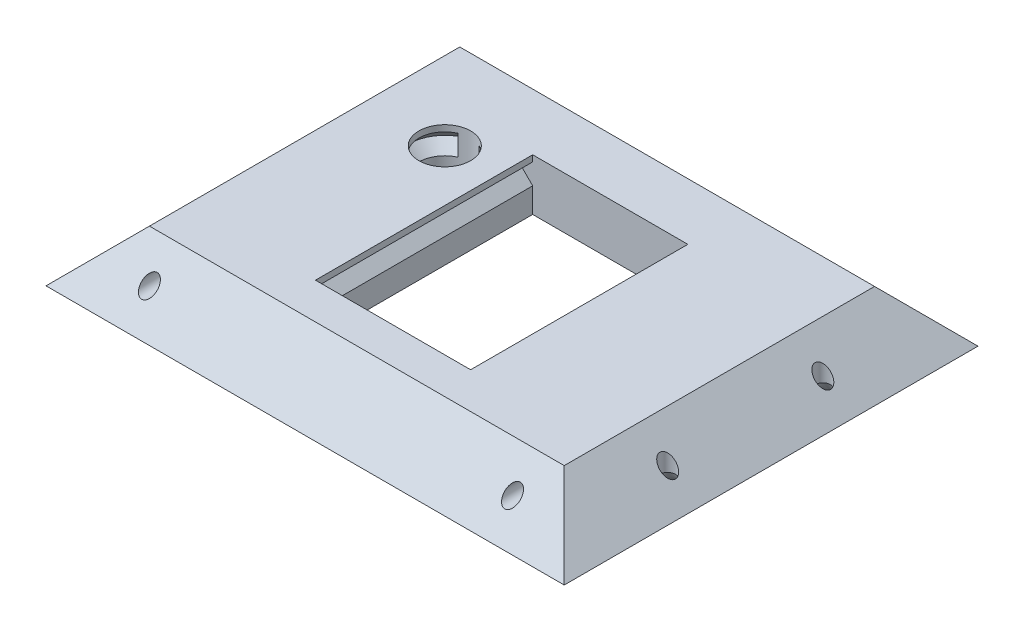
SolidWorks part; units mm, degrees
ref_plane "Спереди" through (0, 0, 0) normal (0, 0, 1) x (1, 0, 0)
ref_plane "Сверху" through (0, 0, 0) normal (0, 1, 0) x (1, 0, 0)
ref_plane "Справа" through (0, 0, 0) normal (1, 0, 0) x (0, 0, -1)
sketch "Эскиз1" plane through (0, 0, 0) normal (0, 1, 0) x (1, 0, 0)
  line L1 (-50.1, -40) -> (50.1, -40)
  line L2 (-50.1, -40) -> (-50.1, 40)
  line L3 (-50.1, 40) -> (50.1, 40)
  line L4 (50.1, -40) -> (50.1, 40)
  line L5 (-50.1, -40) -> (50.1, 40) construction
  line L6 (-50.1, 40) -> (50.1, -40) construction
  point P0 (0, 0)
  dimension "D1" = 100.2
  dimension "D2" = 80
ref_plane "Плоскость1" through (0, 10, 0) normal (0, 1, 0) x (1, 0, 0)
sketch "Эскиз2" plane through (0, 10, 0) normal (0, 1, 0) x (1, 0, 0)
  line L4 (50.1, -40) -> (50.1, 40) construction
  line L5 (-50.1, -40) -> (50.1, -40) construction
  line L6 (-50.1, -40) -> (-50.1, 40) construction
  line L7 (-50.1, 40) -> (50.1, 40) construction
  line L8 (40.1, -30) -> (40.1, 30)
  line L9 (-40.1, -30) -> (40.1, -30)
  line L10 (-40.1, 30) -> (-40.1, -30)
  line L11 (40.1, 30) -> (-40.1, 30)
  line L12 (40.1, -30) -> (40.1, 30)
  line L13 (-40.1, -30) -> (40.1, -30)
  line L14 (-40.1, 30) -> (-40.1, -30)
  line L15 (40.1, 30) -> (-40.1, 30)
  line L16 (50.1, -40) -> (50.1, 40) construction
  line L17 (-50.1, -40) -> (50.1, -40) construction
  line L18 (-50.1, -40) -> (-50.1, 40) construction
  line L19 (-50.1, 40) -> (50.1, 40) construction
  line L20 (-40.1, -30) -> (-50.1, -30) construction
  line L21 (-40.1, -30) -> (-40.1, -40) construction
  line L22 (40.1, -30) -> (40.1, -40) construction
  line L23 (40.1, -30) -> (50.1, -30) construction
  line L24 (40.1, 30) -> (50.1, 30) construction
  line L25 (40.1, 30) -> (40.1, 40) construction
  line L26 (-40.1, 30) -> (-50.1, 30) construction
  line L27 (-40.1, 30) -> (-40.1, 40) construction
  dimension "D1" = 10
loft "По сечениям1" add profiles "Эскиз1", "Эскиз2" connector at (-50.1, 0, -40) connector at (-40.1, 10, -30)
ref_plane "Плоскость2" through (0, 0, 40) normal (0, 0, 1) x (1, 0, 0)
sketch "Эскиз4" plane through (0, 0, 40) normal (0, 0, 1) x (1, 0, 0)
  line L0 (-50.1, 10) -> (-50.1, 0) construction
  line L1 (50.1, 0) -> (50.1, 10) construction
  line L2 (-50.1, 10) -> (50.1, 10) construction
  line L3 (-50.1, 10) -> (50.1, 10) construction
  line L4 (-40.1, 10) -> (-40.1, 0) construction
  line L5 (-50.1, 0) -> (50.1, 0) construction
  line L6 (-30.1, 10) -> (-30.1, 0) construction
  line L7 (-40.1, 5) -> (-30.1, 5) construction
  line L8 (0, 0) -> (0, 10) construction
  circle A0 centre (-35.1, 5) radius 1.5
  circle A1 centre (35.1, 5) radius 1.5
  dimension "D2" = 3
  dimension "D1" = 10
extrude "Вырез-Вытянуть1" cut sketch "Эскиз4" against normal blind 20
mirror "Зеркальное отражение1" about plane through (0, 0, 0) normal (0, 0, 1) of "Вырез-Вытянуть1"
sketch "Эскиз5" plane through (0, 0, 0) normal (0, -1, 0) x (1, 0, 0)
  line L0 (40.1, 30) -> (40.1, -30) construction
  line L1 (-40.1, 30) -> (40.1, 30) construction
  line L2 (40.1, -30) -> (-40.1, -30) construction
  line L3 (-40.1, -30) -> (-40.1, 30) construction
  line L4 (40.1, 30) -> (40.1, -30) construction
  line L5 (-40.1, 30) -> (40.1, 30) construction
  line L6 (40.1, -30) -> (-40.1, -30) construction
  line L7 (-40.1, -30) -> (-40.1, 30) construction
  line L8 (-40.1, 20) -> (-50.1, 20) construction
  line L10 (-50.1, 40) -> (-50.1, -40) construction
  line L11 (-40.1, 10) -> (-50.1, 10) construction
  line L12 (0, -40) -> (0, 40) construction
  line L13 (-50.1, -40) -> (50.1, -40) construction
  line L14 (-50.1, 40) -> (50.1, 40) construction
  line L15 (-50.1, 0) -> (50.1, 0) construction
  line L16 (50.1, 40) -> (50.1, -40) construction
  line L17 (-45.1, 20) -> (-45.1, 10) construction
  circle A0 centre (-45.1, 15) radius 1.5
  circle A1 centre (-45.1, -15) radius 1.5
  circle A2 centre (45.1, -15) radius 1.5
  circle A3 centre (45.1, 15) radius 1.5
  dimension "D3" = 3
  dimension "D1" = 10
  dimension "D2" = 20
extrude "Вырез-Вытянуть2" cut sketch "Эскиз5" against normal through all contours A2 | A3 | A1 | A0
sketch "Sketch1" plane through (0, 0, 0) normal (0, -1, 0) x (1, 0, 0)
  line L0 (-50.1, 0) -> (50.1, 0) construction
  line L1 (-50.1, -40) -> (-50.1, 40) construction
  line L2 (50.1, 40) -> (50.1, -40) construction
  line L3 (0, 40) -> (0, -40) construction
  line L4 (-50.1, 40) -> (50.1, 40) construction
  line L5 (50.1, -40) -> (-50.1, -40) construction
  circle A0 centre (-45.1, 15) radius 3.3
  dimension "D1" = 6.6
ref_plane "Plane1" through (0, 2.8, 0) normal (0, -1, 0) x (-1, 0, 0)
sketch "Sketch2" plane through (0, 2.8, 0) normal (0, -1, 0) x (-1, 0, 0)
  line L0 (50.1, 0) -> (-50.1, 0) construction
  line L1 (50.1, 0) -> (-50.1, 0) construction
  line L2 (0, -40) -> (0, 40) construction
  line L3 (0, -40) -> (0, 40) construction
  circle A0 centre (45.1, -15) radius 1.5 construction
  circle A1 centre (45.1, -15) radius 1.5
ref_plane "Plane2" through (0, 0, 0) normal (0, 0, 1) x (1, 0, 0)
loft "Cut-Loft1" cut profiles "Sketch2", "Sketch1" connector at (-43.9235, 2.8, 15.9305) connector at (-43.8813, 0, 18.0667)
mirror "Mirror1" about plane through (0, 0, 0) normal (0, 0, 1) of "Cut-Loft1"
ref_plane "Plane3" through (0, 0, 0) normal (1, 0, 0) x (0, 0, -1)
mirror "Mirror2" about plane through (0, 0, 0) normal (1, 0, 0) of "Mirror1", "Cut-Loft1"
sketch "Sketch3" plane through (0, 0, 0) normal (0, -1, 0) x (1, 0, 0)
  line L0 (0, 40) -> (0, -40) construction
  line L1 (-50.1, 40) -> (50.1, 40) construction
  line L2 (50.1, -40) -> (-50.1, -40) construction
  line L4 (-15, 23) -> (15, 23)
  line L5 (-15, 23) -> (-15, -19)
  line L6 (-15, -19) -> (15, -19)
  line L7 (15, 23) -> (15, -19)
  line L8 (-15, 23) -> (15, -19) construction
  line L9 (-15, -19) -> (15, 23) construction
  circle A0 centre (-25, -12) radius 5
  point P10 (0, 2)
  dimension "D4" = 10
  dimension "D1" = 30
  dimension "D2" = 42
  dimension "D3" = 21
  dimension "D5" = 10
  dimension "D6" = 28
extrude "Cut-Extrude1" cut sketch "Sketch3" against normal through all
sketch "Sketch4" plane through (0, 0, -19) normal (0, 0, 1) x (1, 0, 0)
  line L0 (0, 0) -> (0, 10) construction
  line L1 (-15, 0) -> (15, 0) construction
  line L2 (15, 10) -> (-15, 10) construction
  line L3 (-15, 8.8) -> (-17, 6.8)
  line L4 (-15, 10) -> (-15, 0) construction
  line L5 (-17, 6.8) -> (-15, 4.8)
  line L6 (-15, 4.8) -> (-15, 8.8)
  line L7 (15, 4.8) -> (15, 8.8)
  line L8 (17, 6.8) -> (15, 4.8)
  line L9 (15, 8.8) -> (17, 6.8)
  dimension "D1" = 1.2
  dimension "D2" = 2
  dimension "D3" = 45
extrude "Cut-Extrude2" cut sketch "Sketch4" along normal up to surface (42 mm away) up to face at (0, 5, 23)
ref_plane "Плоскость3" through (0, 6.8, 0) normal (0, -1, 0) x (-1, 0, 0)
sketch "Эскиз6" plane through (0, 6.8, 0) normal (0, -1, 0) x (-1, 0, 0)
  line L0 (25, 12) -> (25, -2.1051) construction
  line L1 (27, 5.2918) -> (27, 18.7082)
  line L2 (23, 5.2918) -> (23, 18.7082)
  circle A0 centre (25, 12) radius 5 construction
  circle A1 centre (25, 12) radius 5 construction
  arc A2 (27, 5.2918) -> (27, 18.7082) centre (25, 12) ccw
  arc A3 (23, 18.7082) -> (23, 5.2918) centre (25, 12) ccw
  circle A4 centre (25, 12) radius 7 construction
  point P11 (0, 0)
  point P12 (0, 0)
  point P13 (32, 12)
  dimension "D1" = 2
  dimension "D2" = 2
ref_plane "Плоскость4" through (0, 4.8, 0) normal (0, -1, 0) x (-1, 0, 0)
sketch "Эскиз7" plane through (0, 4.8, 0) normal (0, -1, 0) x (-1, 0, 0)
  line L0 (27, 5.2918) -> (27, 18.7082) construction
  line L1 (27, 7.4174) -> (27, 16.5826)
  line L2 (23, 5.2918) -> (23, 18.7082) construction
  line L3 (23, 7.4174) -> (23, 16.5826)
  circle A0 centre (25, 12) radius 5 construction
  arc A1 (27, 7.4174) -> (27, 16.5826) centre (25, 12) ccw
  arc A2 (23, 16.5826) -> (23, 7.4174) centre (25, 12) ccw
loft "Вырез-По сечениям1" cut section "Эскиз6" section "Эскиз7" connector at (-23, 6.8, -5.2918) connector at (-23, 4.8, -7.4174)
loft "Вырез-По сечениям2" cut section "Эскиз6<3>" section "Эскиз7<3>" connector at (-27, 6.8, -5.2918) connector at (-27, 4.8, -7.4174)
sketch "Эскиз6<3>" plane through (0, 6.8, 0) normal (0, -1, 0) x (-1, 0, 0) same geometry as "Эскиз6"
sketch "Эскиз7<3>" plane through (0, 4.8, 0) normal (0, -1, 0) x (-1, 0, 0) same geometry as "Эскиз7"
mirror "Зеркальное отражение2" about plane through (0, 6.8, 0) normal (0, -1, 0) of "Вырез-По сечениям2", "Вырез-По сечениям1"
sketch "Эскиз8" plane through (0, 0, 0) normal (0, -1, 0) x (1, 0, 0)
  line L0 (-35.1, 5) -> (-35.1, -25)
  line L1 (-35.1, -25) -> (-5.1, -25)
  line L2 (-5.1, -25) -> (-5.1, -25.5)
  line L3 (-5.1, -25.5) -> (-4.1, -24.5)
  line L4 (-4.1, -24.5) -> (-5.1, -23.5)
  line L5 (-5.1, -23.5) -> (-5.1, -24)
  line L6 (-5.1, -24) -> (-34.1, -24)
  line L7 (-34.1, -24) -> (-34.1, 5)
  line L8 (-34.1, 5) -> (-33.6, 5)
  line L9 (-33.6, 5) -> (-34.6, 6)
  line L10 (-34.6, 6) -> (-35.6, 5)
  line L11 (-35.6, 5) -> (-35.1, 5)
  line L12 (-34.1, -24) -> (-34.1, -25) construction
  line L13 (-34.1, -24) -> (-35.1, -24) construction
  line L14 (-34.1, -24.5) -> (-4.1, -24.5) construction
  line L15 (-34.6, 6) -> (-34.6, -24) construction
  line L16 (-50.1, -40) -> (-50.1, 40) construction
  line L17 (50.1, -40) -> (-50.1, -40) construction
  dimension "D1" = 1
  dimension "D2" = 0.5
  dimension "D3" = 1
  dimension "D4" = 30
  dimension "D5" = 15
  dimension "D6" = 15
extrude "Вырез-Вытянуть3" cut sketch "Эскиз8" against normal blind 0.6
